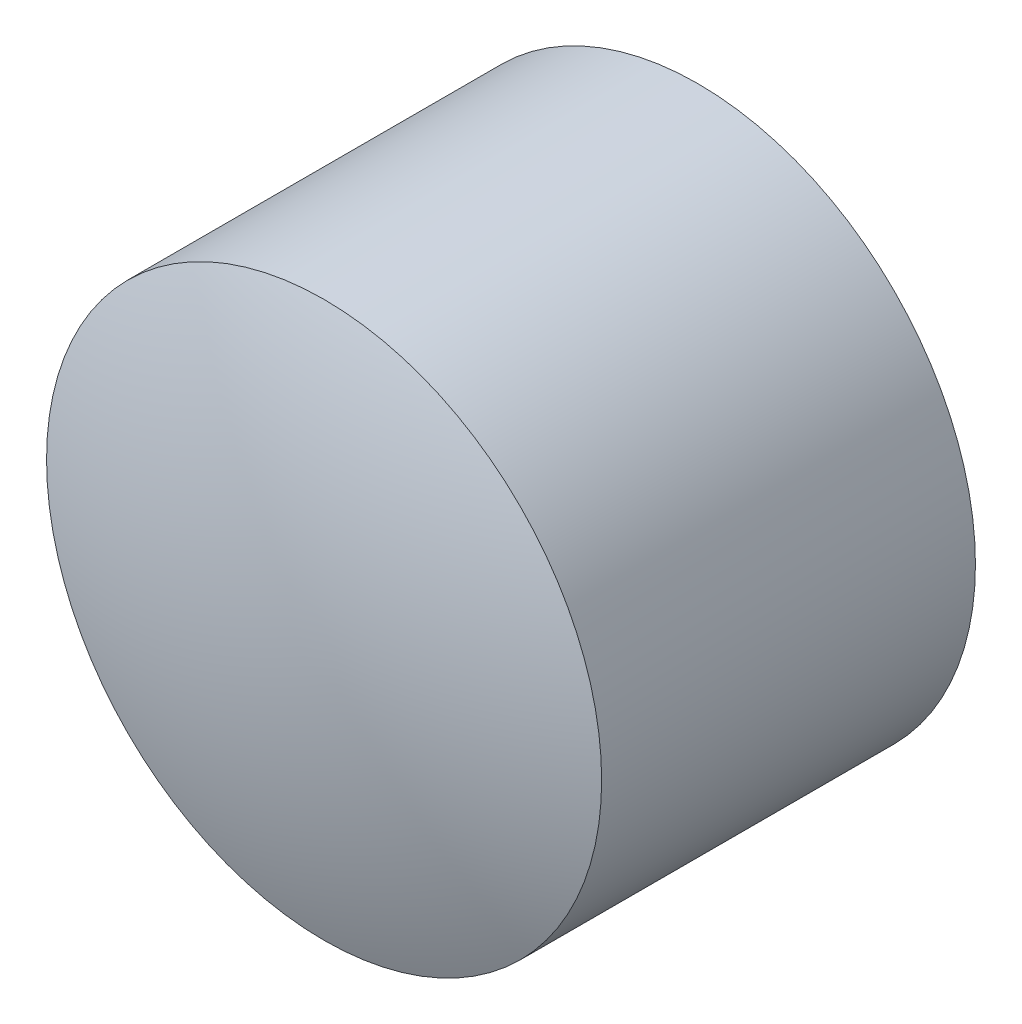
SolidWorks part; units mm, degrees
ref_plane "Front Plane" through (0, 0, 0) normal (0, 0, 1) x (1, 0, 0)
ref_plane "Top Plane" through (0, 0, 0) normal (0, 1, 0) x (1, 0, 0)
ref_plane "Right Plane" through (0, 0, 0) normal (1, 0, 0) x (0, 0, -1)
sketch "Sketch3" plane through (0, 0, 0) normal (1, 0, 0) x (0, 0, -1)
  line L1 (0, 0) -> (0, 3.875)
  line L3 (0, 0) -> (-10, 0)
  line L4 (0, 0) -> (5, 0)
  line L5 (0, 0) -> (4, 0)
  line L6 (0, -3.875) -> (0, 0)
  line L7 (0, 3.875) -> (-5.2187, 3.875)
  line L8 (-5.2187, 3.875) -> (-5.2187, -3.875)
  line L9 (0, -3.875) -> (-5.2187, -3.875)
  arc A2 (0, -3.875) -> (0, 3.875) centre (5, 0) cw
  arc A3 (-5.2187, 3.875) -> (-5.2187, -3.875) centre (5, 0) ccw
  dimension "D2" = 3.875
  dimension "D4" = 10
  dimension "D1" = 5
  dimension "D3" = 4
  dimension "D5" = 3.875
  dimension "D6" = 5.2187
  dimension "D7" = 7.75
  dimension "D8" = 5.2187
revolve "Revolve1" add sketch "Sketch3" angle 360 about L3 region at (0, 2.0343, 3.044) region at (0, 1.4596, 5.5035)
equation "\"T_c\"= \"gloabl_scale\" * 6mm"
equation "\"R_1\"= \"gloabl_scale\" * 5mm"
equation "\"h\"= \"gloabl_scale\" * 7.75 / 2mm"
equation "\"gloabl_scale\"= 1"
equation "\"R_2\"= \"gloabl_scale\" * 10mm"
equation "\"D2@Sketch3\"=\"h\""
equation "\"D4@Sketch3\"=\"R_2\""
equation "\"x_origin_1\"= \"R_1\""
equation "\"x_origin_2\"= \"R_2\" - \"T_c\""
equation "\"T_edge\"= \"T_c\" - \"R_2\" * ( 1 - sqr ( 1 - \"h\" ^ 2 / \"R_2\" ^ 2 ) )"
equation "\"D1@Sketch3\"=\"R_1\""
equation "\"D3@Sketch3\"=\"R_2\"-\"T_c\""
equation "\"D5@Sketch3\"=\"h\""
equation "\"D6@Sketch3\"=\"T_edge\""
equation "\"D7@Sketch3\"=2*\"h\""
equation "\"D8@Sketch3\" = \"T_edge\""
